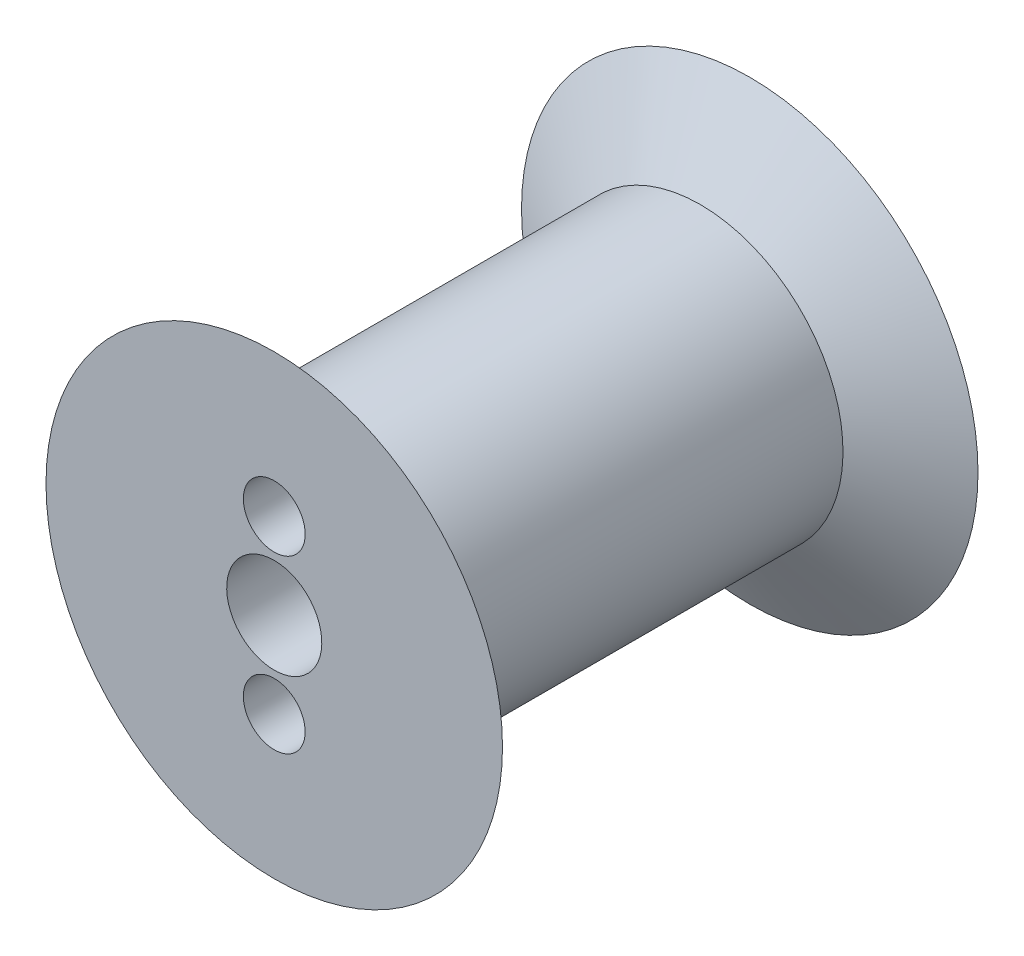
SolidWorks part; units mm, degrees
ref_plane "Front Plane" through (0, 0, 0) normal (0, 0, 1) x (1, 0, 0)
ref_plane "Top Plane" through (0, 0, 0) normal (0, 1, 0) x (1, 0, 0)
ref_plane "Right Plane" through (0, 0, 0) normal (1, 0, 0) x (0, 0, -1)
ref_axis "Axis1" through (0, 0, -62.5) along (0, 0, 1)
ref_plane "Plane1" through (0, 0, 0) normal (0, -1, 0) x (-1, 0, 0)
sketch "Sketch2" plane through (0, 0, 0) normal (0, -1, 0) x (-1, 0, 0)
  line L0 (5, 0) -> (5, -50)
  line L1 (-17.5, 0) -> (17.5, 0) construction
  line L2 (5, -50) -> (24, -50)
  line L3 (24, -50) -> (15, -44.8038)
  line L4 (15, -44.8038) -> (15, -5.1962)
  line L5 (15, -5.1962) -> (24, 0)
  line L6 (24, 0) -> (5, 0)
  line L7 (0, 0) -> (0, -30.254) construction
  dimension "D1" = 30
  dimension "D2" = 10
  dimension "D3" = 30
  dimension "D4" = 10
  dimension "D5" = 50
  dimension "D6" = 24
revolve "Revolve1" add sketch "Sketch2" angle 360 about L7
hole_wizard "CBORE for M3 SHCS1" positions "Sketch3" profile "Sketch5" counterbore size "M3" standard "ANSI Metric" end condition up to next
sketch "Sketch3" plane through (0, 0, 50) normal (0, 0, 1) x (1, 0, 0)
  circle A0 centre (0, -9) radius 1.7 construction
  circle A1 centre (0, 9) radius 1.7 construction
  point P0 (0, -9)
  point P2 (0, 9)
sketch "Sketch5" plane through (0, -9, 50) normal (1, 0, 0) x (0, -1, 0)
  line L0 (0, 0) -> (0, 50)
  line L1 (0, 50) -> (1.7, 50)
  line L3 (1.7, 50) -> (1.7, 40)
  line L4 (1.7, 40) -> (3.25, 40)
  line L5 (3.25, 40) -> (3.25, 0)
  line L7 (3.25, 0) -> (0, 0)
  line L11 (0, -6.35) -> (0, 107.95) construction
  dimension "Thru Hole Dia." = 3.4
  dimension "Thru Hole Depth" = 50
  dimension "C'Bore Dia." = 6.5
  dimension "C'Bore Depth" = 40
